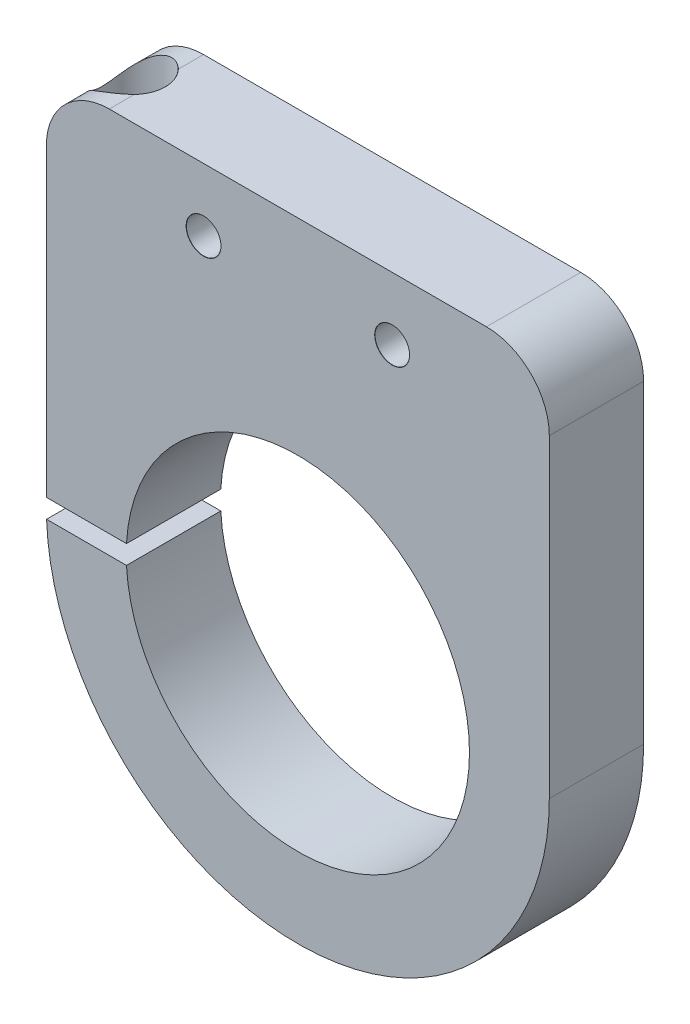
SolidWorks part; units mm, degrees
ref_plane "Front Plane" through (0, 0, 0) normal (0, 0, 1) x (1, 0, 0)
ref_plane "Top Plane" through (0, 0, 0) normal (0, 1, 0) x (1, 0, 0)
ref_plane "Right Plane" through (0, 0, 0) normal (1, 0, 0) x (0, 0, -1)
sketch "Sketch2" plane through (0, 0, 0) normal (0, 0, 1) x (1, 0, 0)
  line L0 (-40, 0) -> (-40, 60)
  line L1 (-40, 60) -> (40, 60)
  line L2 (40, 60) -> (40, 0)
  line L3 (40, 0) -> (-40, 0)
  circle A0 centre (0, 0) radius 40
  circle A1 centre (0, 0) radius 27.3
  dimension "D1" = 54.6
  dimension "D2" = 80
  dimension "D3" = 60
extrude "Boss-Extrude1" add sketch "Sketch2" along normal blind 15 contours A0 L2 L1 L0 | A1 L3 A0 | A1 L3 A0 region at (0, 39.1056, 0) region at (0, 44.3137, 0) region at (-33.65, -0.8944, 0)
sketch "Sketch3" plane through (0, 0, 15) normal (0, 0, 1) x (1, 0, 0)
  line L0 (-40, 0) -> (-40, 60) construction
  line L1 (-40, 1.5) -> (-27.2588, 1.5)
  line L2 (-40, 1.5) -> (-40, -1.5)
  line L3 (-40, -1.5) -> (-27.2588, -1.5)
  line L4 (-27.2588, 1.5) -> (-27.2588, -1.5)
  circle A2 centre (0, 0) radius 27.3 construction
  point P4 (-27.2588, 0)
  dimension "D1" = 3
extrude "Cut-Extrude1" cut sketch "Sketch3" against normal through all
sketch "Sketch11" plane through (0, 60, 0) normal (0, 1, 0) x (1, 0, 0)
  line L1 (-39.9719, -15) -> (-27.2588, -15) construction
  line L2 (-40, -15) -> (-40, 0) construction
  point P0 (-33.6153, -7.5)
  point P10 (-33.6153, -15)
  point P13 (-40, -7.5)
hole_wizard "CBORE for M5 SHCS3" positions "Sketch11" profile "Sketch10" counterbore size "M5" standard "ANSI Metric" end condition through all
sketch "Sketch10" plane through (-33.6153, 60, 7.5) normal (1, 0, 0) x (0, 0, 1)
  line L0 (0, 0) -> (0, 100)
  line L1 (0, 100) -> (2.75, 100)
  line L3 (2.75, 100) -> (2.75, 40)
  line L4 (5, 40) -> (2.75, 40)
  line L5 (5, 40) -> (5, 0.025)
  line L6 (5, 0.025) -> (5.025, 0)
  line L7 (5.025, 0) -> (0, 0)
  line L8 (-5, 0.025) -> (-5.025, 0) construction
  line L11 (0, -6.35) -> (0, 107.95) construction
  dimension "Thru Hole Dia." = 5.5
  dimension "Thru Hole Depth" = 100
  dimension "C'Bore Dia." = 10
  dimension "C'Bore Depth" = 40
  dimension "Near C'Sink Dia." = 10.05
  dimension "Near C'Sink Angle" = 90
sketch "Sketch17" plane through (0, 0, 15) normal (0, 0, 1) x (1, 0, 0)
  line L0 (-15, 50) -> (15, 50) construction
  line L2 (-40, 60) -> (40, 60) construction
  point P0 (-15, 50)
  point P2 (15, 50)
  point P9 (0, 50)
  dimension "D1" = 30
  dimension "D2" = 10
hole_wizard "M5 Clearance Hole1" positions "Sketch17" profile "Sketch15" hole size "M5" standard "ANSI Metric" end condition through all
sketch "Sketch15" plane through (-15, 50, 15) normal (1, 0, 0) x (0, -1, 0)
  line L0 (0, 0) -> (0, 15)
  line L1 (0, 15) -> (2.75, 15)
  line L2 (2.75, 15) -> (2.75, 0.025)
  line L3 (2.75, 0.025) -> (2.775, 0)
  line L5 (2.775, 0) -> (0, 0)
  line L6 (-2.75, 0.025) -> (-2.775, 0) construction
  line L11 (0, -6.35) -> (0, 107.95) construction
  dimension "Thru Hole Dia." = 5.5
  dimension "Thru Hole Depth" = 15
  dimension "Near C'Sink Dia." = 5.55
  dimension "Near C'Sink Angle" = 90
fillet "Fillet1" radius 10 2 edges at (-40, 60, 7.5) (40, 60, 7.5)
ref_plane "Plane1" through (0, -16.5, 0) normal (0, 1, 0) x (1, 0, 0)
sketch "Sketch18" plane through (0, -16.5, 0) normal (0, 1, 0) x (1, 0, 0)
  line L1 (-28.881, -7.5) -> (-31.2482, -3.4)
  line L2 (-31.2482, -3.4) -> (-35.9824, -3.4)
  line L3 (-35.9824, -3.4) -> (-38.3496, -7.5)
  line L4 (-38.3496, -7.5) -> (-35.9824, -11.6)
  line L5 (-35.9824, -11.6) -> (-31.2482, -11.6)
  line L6 (-31.2482, -11.6) -> (-28.881, -7.5)
  circle A0 centre (-33.6153, -7.5) radius 4.1 construction
  circle A1 centre (-33.6153, -7.5) radius 2.75 construction
  point P15 (-33.6153, -3.4)
  dimension "D1" = 8.2
extrude "Cut-Extrude2" cut sketch "Sketch18" against normal through all
